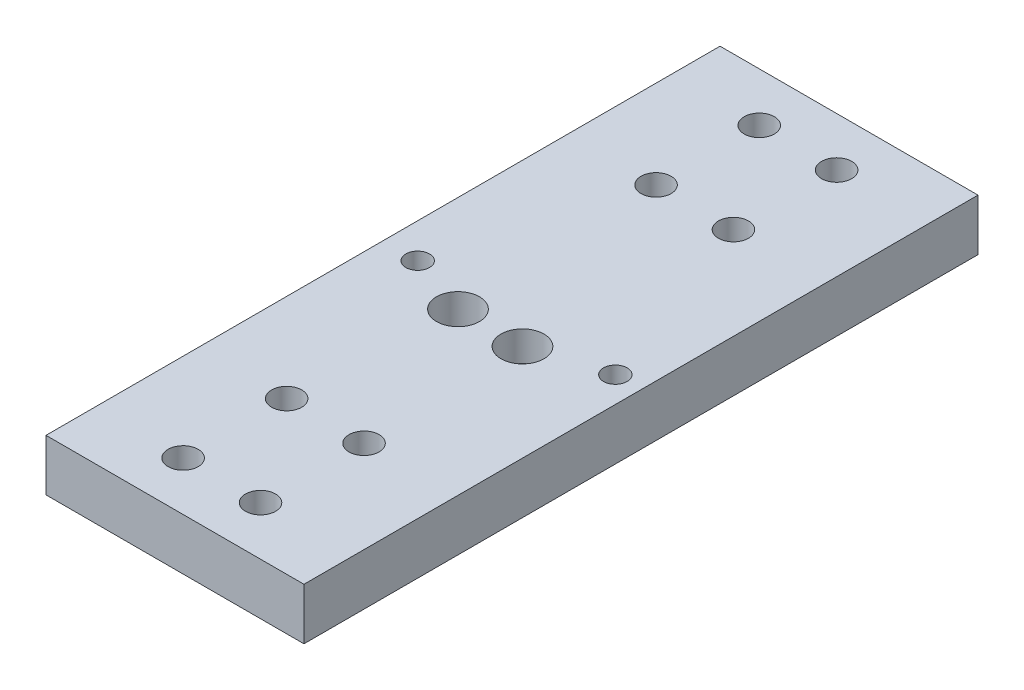
SolidWorks part; units mm, degrees
ref_plane "Front Plane" through (0, 0, 0) normal (0, 0, 1) x (1, 0, 0)
ref_plane "Top Plane" through (0, 0, 0) normal (0, 1, 0) x (1, 0, 0)
ref_plane "Right Plane" through (0, 0, 0) normal (1, 0, 0) x (0, 0, -1)
sketch "Sketch3" plane through (-27.527, 0, 0) normal (0, 1, 0) x (0, 0, 1)
  line L0 (41.3041, 73.5608) -> (-72.5469, 73.5608) construction
  line L2 (41.3041, 8.3895) -> (-72.5469, 8.3895) construction
  line L3 (31.3041, -26.6984) -> (31.3041, 62.3179) construction
  line L5 (-78.6959, -26.6984) -> (-78.6959, 62.3179) construction
  line L7 (31.3041, 62.3179) -> (-78.6959, -26.6984) construction
  line L13 (54.6906, 47.8098) -> (-102.0824, 47.8098)
  line L14 (54.6906, 47.8098) -> (54.6906, -12.1902)
  line L15 (54.6906, -12.1902) -> (-102.0824, -12.1902)
  line L16 (-102.0824, 47.8098) -> (-102.0824, -12.1902)
  line L17 (54.6906, 47.8098) -> (-102.0824, -12.1902) construction
  line L18 (54.6906, -12.1902) -> (-102.0824, 47.8098) construction
  point P2 (-23.6959, 17.8098)
  dimension "D1" = 60
extrude "Boss-Extrude6" add sketch "Sketch3" along normal blind 12
sketch "Sketch4" plane through (0, 12, 0) normal (0, 1, 0) x (1, 0, 0)
  line L0 (20.2828, 23.6959) -> (-39.7172, 23.6959) construction
  line L1 (20.2828, -54.6906) -> (20.2828, 102.0824) construction
  line L2 (-39.7172, 102.0824) -> (-39.7172, -54.6906) construction
  line L3 (20.2828, -31.3041) -> (-39.7172, -31.3041) construction
  line L4 (20.2828, 78.6959) -> (-39.7172, 78.6959) construction
  line L5 (-10.2465, -54.6906) -> (-9.7172, 102.0824) construction
  line L6 (-39.7172, -54.6906) -> (20.2828, -54.6906) construction
  line L7 (20.2828, 102.0824) -> (-39.7172, 102.0824) construction
  line L8 (20.2828, -43.3041) -> (-39.7172, -43.3041) construction
  line L9 (20.2828, -19.3041) -> (-39.7172, -19.3041) construction
  line L10 (-39.7172, 66.6959) -> (20.2828, 66.6959) construction
  line L11 (-39.7172, 90.6959) -> (20.2828, 90.6959) construction
  line L12 (-19.2081, -43.3041) -> (-19.2081, 106.6241) construction
  line L13 (-1.208, -43.3041) -> (-1.208, 116.9979) construction
  circle A2 centre (-1.127, -19.3041) radius 2.25
  circle A3 centre (-19.1271, -19.3041) radius 2.25
  circle A4 centre (-1.208, -43.3041) radius 2.25
  circle A5 centre (-19.2081, -43.3041) radius 2.25
  circle A6 centre (-19.2081, 66.6959) radius 2.25
  circle A7 centre (-19.2081, 90.6959) radius 2.25
  circle A8 centre (-1.208, 90.6959) radius 2.25
  circle A9 centre (-1.208, 66.6959) radius 2.25
  dimension "D5" = 9
  dimension "D9" = 4.5
  dimension "D12" = 4.5
  dimension "D1" = 55
  dimension "D2" = 55
  dimension "D3" = 12
  dimension "D4" = 12
  dimension "D6" = 9
  dimension "D7" = 9
  dimension "D8" = 9
  dimension "D10" = 12
  dimension "D11" = 12
extrude "Cut-Extrude1" cut sketch "Sketch4" against normal up to next
sketch "Sketch6" plane through (0, 12, 0) normal (0, 1, 0) x (1, 0, 0)
  line L3 (-9.7172, -54.6906) -> (-9.7172, 102.0824) construction
  line L4 (-39.7172, -54.6906) -> (20.2828, -54.6906) construction
  line L5 (20.2828, 102.0824) -> (-39.7172, 102.0824) construction
  line L6 (-17.2172, 18.6316) -> (-2.2172, 18.6316) construction
  circle A0 centre (-17.2172, 18.6316) radius 3.25
  circle A1 centre (-2.2172, 18.6316) radius 3.25
  point P0 (-9.7172, 18.6316)
  dimension "D1" = 6.5
  dimension "D2" = 6.5
  dimension "D3" = 15
  dimension "D4" = 73.3222
extrude "Cut-Extrude2" cut sketch "Sketch6" against normal up to next
sketch "Sketch7" plane through (0, 12, 0) normal (0, 1, 0) x (1, 0, 0)
  circle A0 centre (-19.1271, -19.3041) radius 3.5
  circle A1 centre (-19.2081, -43.3041) radius 3.5
  circle A2 centre (-1.208, -43.3041) radius 3.5
  circle A3 centre (-1.127, -19.3041) radius 3.5
  circle A4 centre (-1.208, 66.6959) radius 3.5
  circle A5 centre (-19.2081, 66.6959) radius 3.5
  circle A6 centre (-19.2081, 90.6959) radius 3.5
  circle A7 centre (-1.208, 90.6959) radius 3.5
  dimension "D1" = 7
extrude "Cut-Extrude3" cut sketch "Sketch7" against normal blind 5
sketch "Sketch8" plane through (0, 12, 0) normal (0, 1, 0) x (1, 0, 0)
  circle A0 centre (-17.2172, 18.6316) radius 5
  circle A1 centre (-2.2172, 18.6316) radius 5
  dimension "D1" = 10
  dimension "D2" = 10
extrude "Cut-Extrude4" cut sketch "Sketch8" against normal blind 7
sketch "Sketch9" plane through (0, 12, 0) normal (0, 1, 0) x (1, 0, 0)
  circle A0 centre (-31.6579, 23.7018) radius 2.75
  circle A1 centre (14.2827, 23.7357) radius 2.75
  dimension "D1" = 5.5
extrude "Cut-Extrude5" cut sketch "Sketch9" against normal up to next
